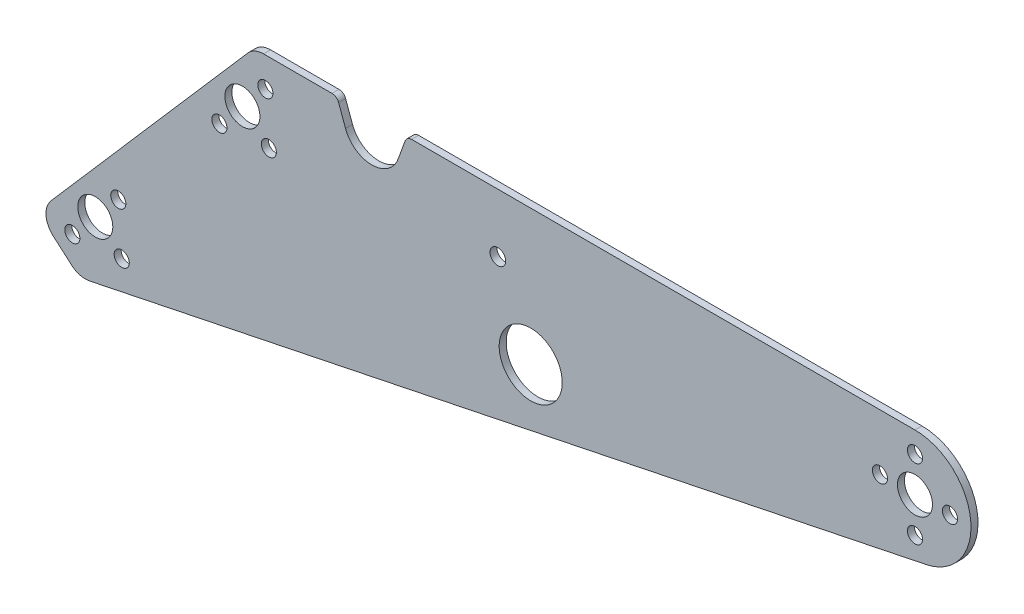
SolidWorks part; units mm, degrees
material "6061-T6 (SS)"
ref_plane "Front Plane" through (0, 0, 0) normal (0, 0, 1) x (1, 0, 0)
ref_plane "Top Plane" through (0, 0, 0) normal (0, 1, 0) x (1, 0, 0)
ref_plane "Right Plane" through (0, 0, 0) normal (1, 0, 0) x (0, 0, -1)
sketch "Sketch1" plane through (0, 0, 0) normal (0, 0, 1) x (1, 0, 0)
  line L0 (0, 0) -> (-66.6556, -76.6785) construction
  line L1 (55, 0) -> (-55, 0) construction
  line L2 (304.8, 25.4) -> (76.7244, 25.4)
  line L3 (-86.6553, -80.3276) -> (2.4044, 22.124)
  line L4 (-69.2153, -103.1424) -> (309.935, -24.8755)
  line L5 (0, 15.875) -> (0, -15.875) construction
  line L6 (-15.875, 0) -> (15.875, 0) construction
  line L7 (-66.6556, -76.6785) -> (-56.2407, -64.6975) construction
  line L8 (-66.6556, -76.6785) -> (-54.6746, -87.0934) construction
  line L9 (-85.7157, -93.7651) -> (-77.3898, -101.0027)
  line L10 (304.8, 0) -> (304.8, 15.875) construction
  line L11 (0, 0) -> (-10.4149, -11.981) construction
  line L12 (0, 0) -> (11.981, -10.4149) construction
  line L13 (70.609, 14.7063) -> (73.7408, 23.3109)
  line L14 (46.7408, 14.7063) -> (43.609, 23.3109)
  line L15 (40.6255, 25.4) -> (9.593, 25.4)
  circle A0 centre (304.8, 0) radius 7.9375
  circle A1 centre (0, 0) radius 7.9375
  circle A2 centre (-66.6556, -76.6785) radius 7.9375
  arc A7 (304.8, 25.4) -> (309.935, -24.8755) centre (304.8, 0) cw
  arc A8 (-69.2153, -103.1424) -> (-77.3898, -101.0027) centre (-71.1409, -93.8141) cw
  arc A17 (-85.7157, -93.7651) -> (-86.6553, -80.3276) centre (-79.4667, -86.5765) cw
  arc A18 (9.593, 25.4) -> (2.4044, 22.124) centre (9.593, 15.875) ccw
  circle A19 centre (304.8, 0) radius 15.875 construction
  circle A20 centre (304.8, 15.875) radius 3.429
  circle A21 centre (320.675, 0) radius 3.429
  circle A22 centre (304.8, -15.875) radius 3.429
  circle A23 centre (288.925, 0) radius 3.429
  circle A24 centre (-66.6556, -76.6785) radius 15.875 construction
  circle A25 centre (-56.2407, -64.6975) radius 3.429
  circle A26 centre (-54.6746, -87.0934) radius 3.429
  circle A27 centre (-77.0705, -88.6595) radius 3.429
  circle A28 centre (0, 0) radius 15.875 construction
  circle A29 centre (-10.4149, -11.981) radius 3.429
  circle A30 centre (11.981, -10.4149) radius 3.429
  circle A31 centre (10.4149, 11.981) radius 3.429
  circle A32 centre (130.6713, -35.9449) radius 14.2875
  arc A33 (46.7408, 14.7063) -> (70.609, 14.7063) centre (58.6749, 19.05) ccw
  arc A34 (43.609, 23.3109) -> (40.6255, 25.4) centre (40.6255, 22.225) ccw
  arc A35 (73.7408, 23.3109) -> (76.7244, 25.4) centre (76.7244, 22.225) cw
  circle A36 centre (115.7866, -1.0874) radius 3.556
  point P21 (0, 0)
  point P26 (0, 0)
  point P64 (42.8487, 25.4)
  dimension "D2" = 15.875
  dimension "D5" = 101.6
  dimension "D6" = 25.4
  dimension "D8" = 6.858
  dimension "D15" = 9.525
  dimension "D16" = 31.75
  dimension "D17" = 4
  dimension "D10" = 31.75
  dimension "D11" = 3
  dimension "D20" = 31.75
  dimension "D21" = 3
  dimension "D24" = 25.4
  dimension "D26" = 28.575
  dimension "D27" = 48.26
  dimension "D31" = 25.4
  dimension "D32" = 3.175
  dimension "D33" = 7.112
  dimension "D35" = 37.9025
  dimension "D3" = 304.8
  dimension "D4" = 131
  dimension "D7" = 31.75
  dimension "D9" = 31.75
  dimension "D12" = 25.4
  dimension "D13" = 12.7
  dimension "D14" = 25.4
  dimension "D18" = 90
  dimension "D19" = 15.875
  dimension "D22" = 90
  dimension "D23" = 15.875
  dimension "D25" = 177.8
  dimension "D28" = 6.35
  dimension "D29" = 110
  dimension "D30" = 110
  dimension "D34" = 26.4874
extrude "Boss-Extrude1" add sketch "Sketch1" along normal blind 3.175
